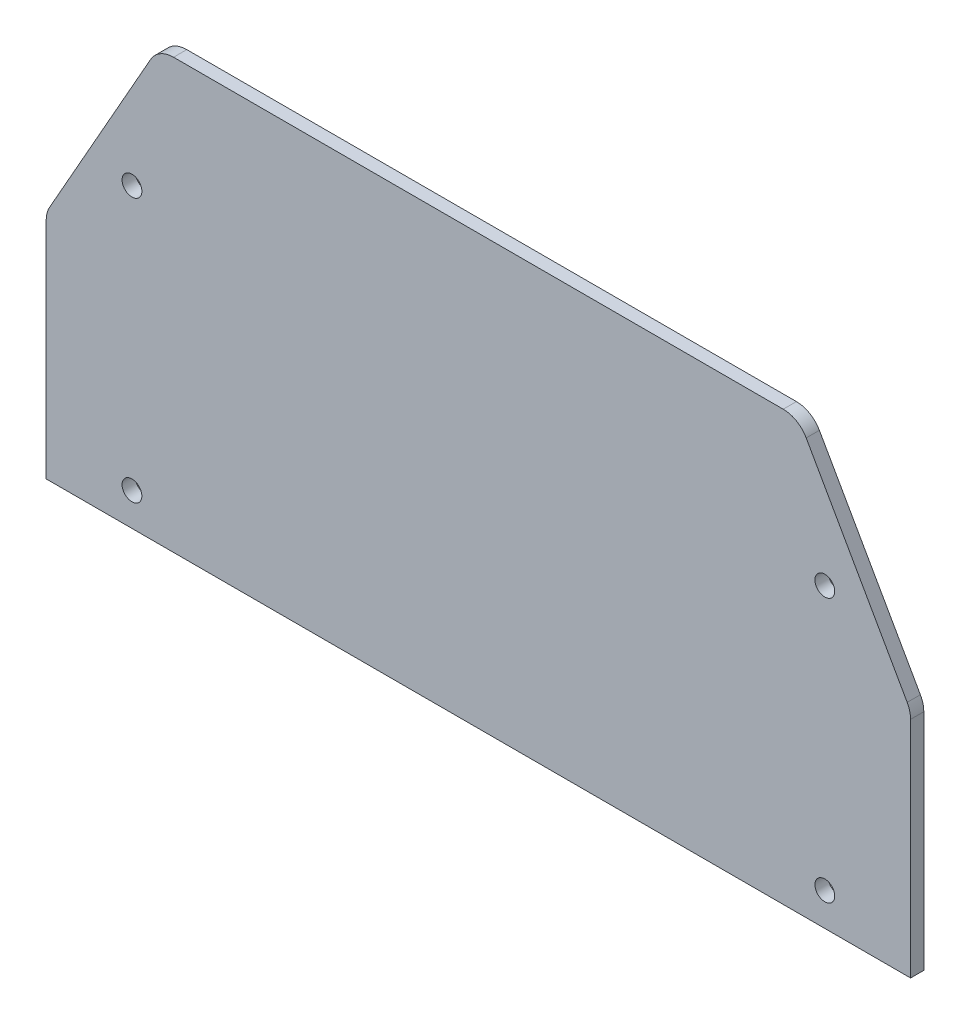
SolidWorks part; units mm, degrees
material "3.3535 (EN-AW 5754)"
ref_plane "Front" through (0, 0, 0) normal (0, 0, 1) x (1, 0, 0)
ref_plane "Top" through (0, 0, 0) normal (0, 1, 0) x (1, 0, 0)
ref_plane "Right" through (0, 0, 0) normal (1, 0, 0) x (0, 0, -1)
sketch "Esquisse1" plane through (0, 0, 0) normal (0, 0, 1) x (1, 0, 0)
  line L0 (-48.5268, 65) -> (-65.5, 35)
  line L1 (-48.5268, 65) -> (48.5268, 65)
  line L2 (-65.5, 35) -> (-65.5, 0)
  line L3 (-65.5, 0) -> (65.5, 0)
  line L4 (0, 65) -> (0, 0) construction
  line L5 (65.5, 35) -> (65.5, 0)
  line L6 (48.5268, 65) -> (65.5, 35)
  circle A0 centre (-52.5, 45) radius 1.5
  circle A1 centre (-52.5, 5) radius 1.5
  circle A2 centre (52.5, 5) radius 1.5
  circle A3 centre (52.5, 45) radius 1.5
  point P10 (0, 0)
  point P11 (0, 0)
  dimension "D1" = 3
  dimension "D2" = 105
  dimension "D4" = 5
  dimension "D5" = 45
  dimension "D3" = 131
  dimension "D6" = 29.5
  dimension "D7" = 65
  dimension "D8" = 35
  dimension "D9" = 16.9732
base flange "Tôle de base pliée1" sketch "Esquisse1" thickness 2 reverse thickness direction no parameters "D1"=1
fillet "Congé1" radius 4 4 edges at (65.5, 35, -1) (48.5268, 65, -1) (-48.5268, 65, -1) (-65.5, 35, -1)
sketch "Lignes de pliage1" [suppressed] plane through (0, 0, 0) normal (0, 1, 0) x (1, 0, 0)
sketch "Cube de visualisation1" [suppressed] plane through (0, 0, 0) normal (0, 1, 0) x (1, 0, 0)
sheet metal parameters "Tôlerie1" thickness 2 parameters "D1"=1
flat pattern "Etat déplié1" [suppressed]
sketch "Lignes de pliage2" plane through (0, 0, 0) normal (0, 1, 0) x (1, 0, 0)
sketch3d "Cube de visualisation2" [suppressed]
  line L0 (-65.5, 65, 0) -> (65.5, 65, 0) construction
  line L1 (-65.5, 0, 0) -> (65.5, 0, 0) construction
  line L2 (-65.5, 65, 0) -> (-65.5, 0, 0) construction
  line L3 (65.5, 65, 0) -> (65.5, 0, 0) construction
